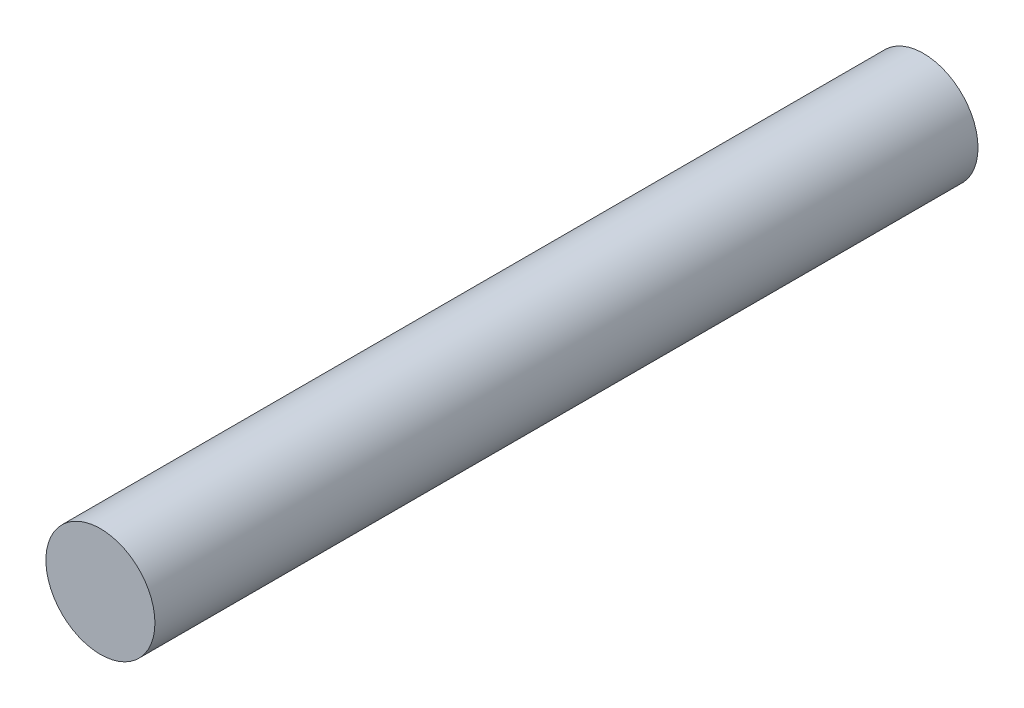
SolidWorks part; units mm, degrees
ref_plane "Front Plane" through (0, 0, 0) normal (0, 0, 1) x (1, 0, 0)
ref_plane "Top Plane" through (0, 0, 0) normal (0, 1, 0) x (1, 0, 0)
ref_plane "Right Plane" through (0, 0, 0) normal (1, 0, 0) x (0, 0, -1)
sketch "Sketch1" plane through (0, 0, 0) normal (0, 0, 1) x (1, 0, 0)
  circle A0 centre (0, 0) radius 2.54
  dimension "D1" = 5.08
extrude "Boss-Extrude1" add sketch "Sketch1" along normal blind 38.35
